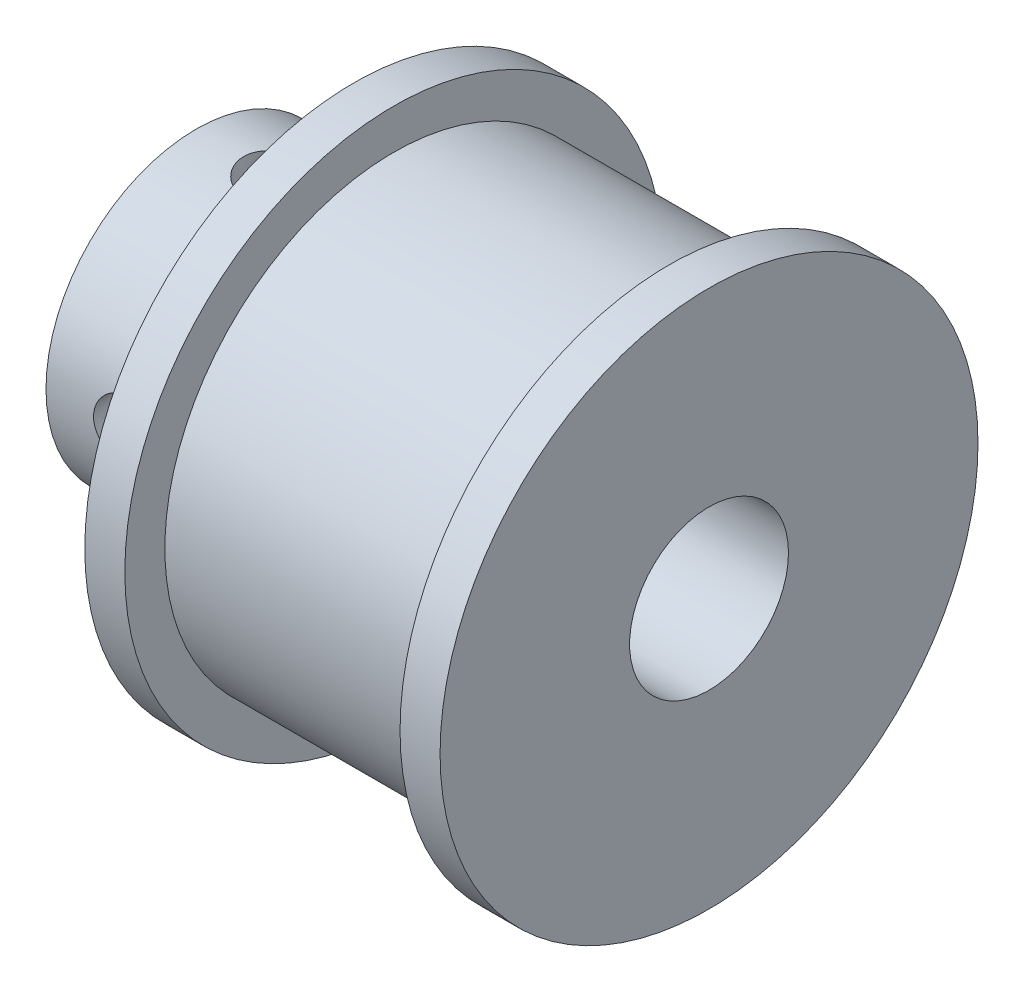
SolidWorks part; units mm, degrees
material "6061-T6 (SS)"
ref_plane "Front Plane" through (0, 0, 0) normal (0, 0, 1) x (1, 0, 0)
ref_plane "Top Plane" through (0, 0, 0) normal (0, 1, 0) x (1, 0, 0)
ref_plane "Right Plane" through (0, 0, 0) normal (1, 0, 0) x (0, 0, -1)
sketch "Sketch1" plane through (0, 0, 0) normal (0, 0, 1) x (1, 0, 0)
  line L0 (0, 3.175) -> (0, 6)
  line L1 (6.3, 10.75) -> (7.9, 10.75)
  line L2 (7.9, 10.75) -> (7.9, 9.15)
  line L3 (7.9, 9.15) -> (18.9, 9.15)
  line L4 (18.9, 9.15) -> (18.9, 10.75)
  line L5 (18.9, 10.75) -> (20.5, 10.75)
  line L6 (20.5, 10.75) -> (20.5, 3.175)
  line L7 (20.5, 3.175) -> (0, 3.175)
  line L8 (0, 0) -> (-7.6744, 0) construction
  line L9 (6.3, 10.75) -> (6.3, 6)
  line L10 (6.3, 6) -> (0, 6)
  dimension "D1" = 6.35
  dimension "D2" = 21.5
  dimension "D3" = 18.3
  dimension "D4" = 14.2
  dimension "D5" = 20.5
  dimension "D6" = 1.6
  dimension "D7" = 12
revolve "Revolve1" add sketch "Sketch1" angle 360 about L8
hole_wizard "M3x0.5 Tapped Hole1" positions "Sketch3" profile "Sketch2" tap size "M3x0.5" standard "ANSI Metric" end condition through all
sketch "Sketch3" plane through (0, 0, 0) normal (0, 1, 0) x (1, 0, 0)
  line L0 (0, 0) -> (6.3, 0) construction
  line L2 (6.3, 6) -> (6.3, -6) construction
  point P8 (3.15, 0)
sketch "Sketch2" plane through (3.15, 0, 0) normal (1, 0, 0) x (0, 0, -1)
  line L0 (0, 0) -> (0, 10.75)
  line L1 (0, 10.75) -> (1.25, 10.75)
  line L2 (1.25, 10.75) -> (1.25, 0)
  line L5 (1.25, 0) -> (0, 0)
  line L11 (0, -6.35) -> (0, 107.95) construction
  dimension "Thread Major Dia." = 2.5
  dimension "Thru Tap Drill Depth" = 10.75
hole_wizard "M3x0.5 Tapped Hole2" positions "Sketch5" profile "Sketch4" tap size "M3x0.5" standard "ANSI Metric" end condition through all
sketch "Sketch5" plane through (0, 0, 0) normal (0, 0, 1) x (1, 0, 0)
  line L0 (0, 0) -> (6.3, 0) construction
  line L2 (6.3, 10.75) -> (6.3, -10.75) construction
  point P7 (3.15, 0)
sketch "Sketch4" plane through (3.15, 0, 0) normal (1, 0, 0) x (0, 1, 0)
  line L0 (0, 0) -> (0, 10.75)
  line L1 (0, 10.75) -> (1.25, 10.75)
  line L2 (1.25, 10.75) -> (1.25, 0)
  line L5 (1.25, 0) -> (0, 0)
  line L11 (0, -6.35) -> (0, 107.95) construction
  dimension "Thread Major Dia." = 2.5
  dimension "Thru Tap Drill Depth" = 10.75
